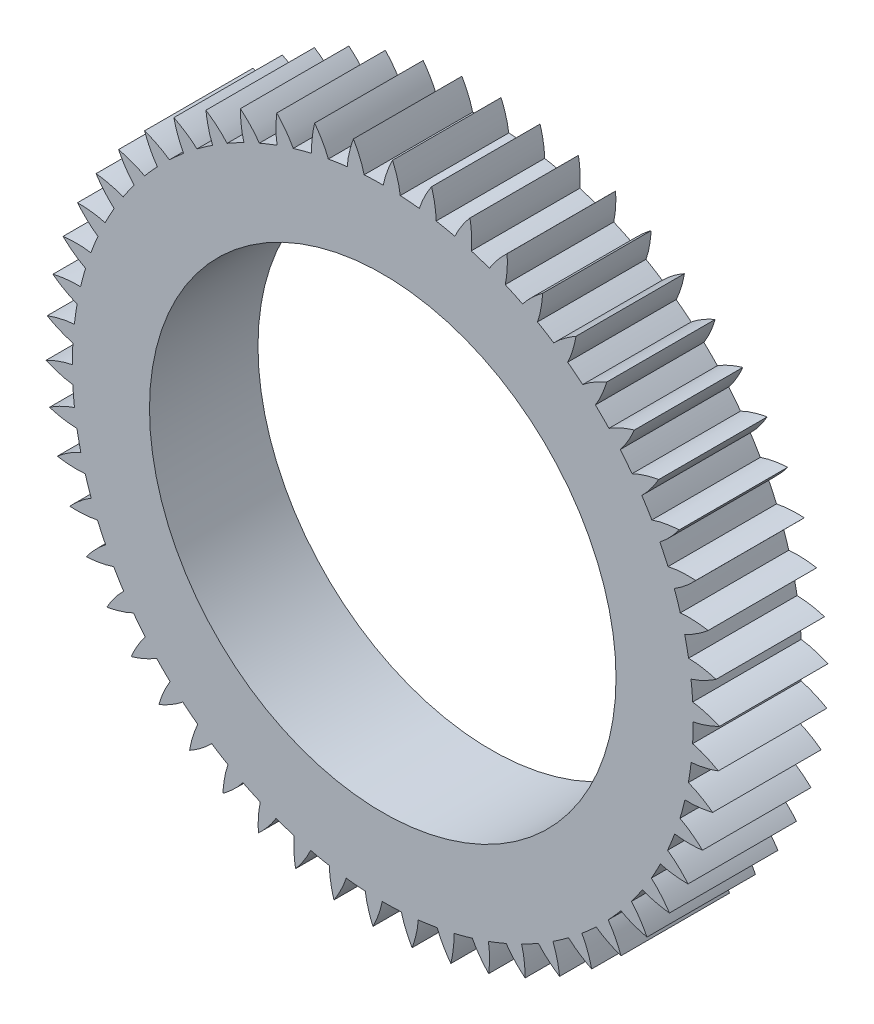
SolidWorks part; units mm, degrees
ref_plane "Front Plane" through (0, 0, 0) normal (0, 0, 1) x (1, 0, 0)
ref_plane "Top Plane" through (0, 0, 0) normal (0, 1, 0) x (1, 0, 0)
ref_plane "Right Plane" through (0, 0, 0) normal (1, 0, 0) x (0, 0, -1)
sketch "Sketch1" plane through (0, 0, 0) normal (0, 0, 1) x (1, 0, 0)
  line L0 (0, 0) -> (62.1959, -1.8097) construction
  line L1 (0, 0) -> (62.1959, 1.8097) construction
  line L2 (0, 0) -> (62.1959, -1.8097) construction
  line L3 (0, 0) -> (62.2222, 0) construction
  line L4 (0, 0) -> (61.9854, 5.423) construction
  line L6 (62.1959, 1.8097) -> (42.9818, 1.2506)
  line L7 (57.198, -1.6643) -> (42.9818, -1.2506)
  circle A0 centre (0, 0) radius 60 construction
  circle A1 centre (0, 0) radius 57.2222 construction
  circle A2 centre (0, 0) radius 56.3816 construction
  circle A3 centre (0, 0) radius 62.2222 construction
  arc A4 (57.2175, 0.7341) -> (57.198, -1.6643) centre (0, 0) cw
  arc A5 (42.9818, -1.2506) -> (42.9818, 1.2506) centre (0, 0) ccw
  arc A6 (62.1941, 1.8705) -> (62.1959, 1.8097) centre (0, 0) ccw
  spline S0 degree 4 poles (56.3816, 0) (56.4651, 0.0025) (56.699, 0.0173) (57.1389, 0.0757) (57.85, 0.214) (58.7435, 0.4527) (59.8791, 0.832) (61.1875, 1.368) (62.5891, 2.0488) (64.069, 2.8851) (65.5016, 3.8027) (66.8858, 4.7917) (68.2223, 5.8442) (69.7865, 7.1909) (71.585, 8.913) (73.5628, 11.056) (75.6559, 13.6606) (77.611, 16.4463) (79.3928, 19.3457) (80.8034, 21.9677) (81.9089, 24.2676) (82.762, 26.2144) (83.4043, 27.79) (84.0064, 29.379) (84.5697, 30.9865) (85.0928, 32.6001) (85.5792, 34.2375) (86.0244, 35.8662) (86.4369, 37.5373) (86.8035, 39.1614) (87.1061, 40.6795) (87.3201, 41.8405) (87.5125, 42.9995) (87.6079, 43.6062) (87.7326, 44.4454) (87.8218, 45.0963) (87.9167, 45.8228) (87.999, 46.5085) (88.0792, 47.2198) (88.1508, 47.9156) (88.2015, 48.4472) (88.2325, 48.7971) (88.2478, 48.9732) knots 0 0 0 0 0 0.005377 0.015084 0.028532 0.04661 0.064855 0.092111 0.119476 0.146842 0.174209 0.201575 0.228941 0.256307 0.307035 0.361767 0.4165 0.471232 0.525964 0.580697 0.608063 0.635429 0.662795 0.690161 0.717528 0.744894 0.77226 0.799626 0.826992 0.854358 0.881725 0.895408 0.909091 0.920455 0.931818 0.943182 0.954545 0.965909 0.977273 0.988636 1 1 1 1 1 construction
  spline S1 degree 4 poles (56.3816, 0) (56.4651, 0.0025) (56.699, 0.0173) (57.1389, 0.0757) (57.85, 0.214) (58.7435, 0.4527) (59.8791, 0.832) (61.1875, 1.368) (62.5891, 2.0488) (64.069, 2.8851) (65.5016, 3.8027) (66.8858, 4.7917) (68.2223, 5.8442) (69.7865, 7.1909) (71.585, 8.913) (73.5628, 11.056) (75.6559, 13.6606) (77.611, 16.4463) (79.3928, 19.3457) (80.8034, 21.9677) (81.9089, 24.2676) (82.762, 26.2144) (83.4043, 27.79) (84.0064, 29.379) (84.5697, 30.9865) (85.0928, 32.6001) (85.5792, 34.2375) (86.0244, 35.8662) (86.4369, 37.5373) (86.8035, 39.1614) (87.1061, 40.6795) (87.3201, 41.8405) (87.4794, 42.8002) (87.5396, 43.1752) (87.5695, 43.3661) knots 0 0 0 0 0 0.005377 0.015084 0.028532 0.04661 0.064855 0.092111 0.119476 0.146842 0.174209 0.201575 0.228941 0.256307 0.307035 0.361767 0.4165 0.471232 0.525964 0.580697 0.608063 0.635429 0.662795 0.690161 0.717528 0.744894 0.77226 0.799626 0.826992 0.854358 0.881725 0.895408 0.909091 0.909091 0.909091 0.909091 0.909091
  point P6 (56.3816, 0)
  dimension "pitchRadius" = 60
  dimension "addendumRadius" = 62.2222
  dimension "dedendumRadius" = 57.2222
  dimension "baseRadius" = 56.3816
  dimension "D1" = 3.333
  dimension "D2" = 1.667
  dimension "toothArc" = 6.667
  dimension "D3" = 43
extrude "Boss-Extrude1" add sketch "Sketch1" along normal blind 20 contours S1 region at (51.2583, 0.1102, 0)
mirror "Mirror1" about plane through (0, 0, 20) normal (0.0291, -0.9996, 0) of "Boss-Extrude1"
pattern_circular "CirPattern2" count 54 over 360 about axis through (0, 0, 20) along (0, 0, -1) of "Boss-Extrude1", "Mirror1"
ref_axis "Axis1" through (0, 0, 0) along (0, 0, 1)
equation "\"D2@Sketch1\"=\"toothArc@Sketch1\"/4"
equation "\"pitchRadius\"= 6"
equation "\"nTeeth\"= 54"
equation "\"pressureAngle\"= 20"
equation "\"baseRadius\"= \"pitchRadius\" * cos ( \"pressureAngle\" )"
equation "\"diametralPitch\"= \"nTeeth\" / ( 2 * \"pitchRadius\" )'note units: cm^-1"
equation "\"dedendum\"= 1.25 / \"diametralPitch\"'for full depth, 20 deg pressure angle"
equation "\"addendum\"= 1 / \"diametralPitch\""
equation "\"pitchRadius@Sketch1\"= \"pitchRadius\""
equation "\"addendumRadius@Sketch1\"= \"pitchRadius\" + \"addendum\""
equation "\"dedendumRadius@Sketch1\"= \"pitchRadius\" - \"dedendum\""
equation "\"baseRadius@Sketch1\"= \"baseRadius\""
equation "\"toothArc@Sketch1\"=360/\"nTeeth\""
equation "\"D2@CirPattern2\"=\"nTeeth\""
equation "\"D1@CirPattern2\"= \"nTeeth\""
equation "\"D1@Sketch1\"=\"toothArc@Sketch1\"/2"
